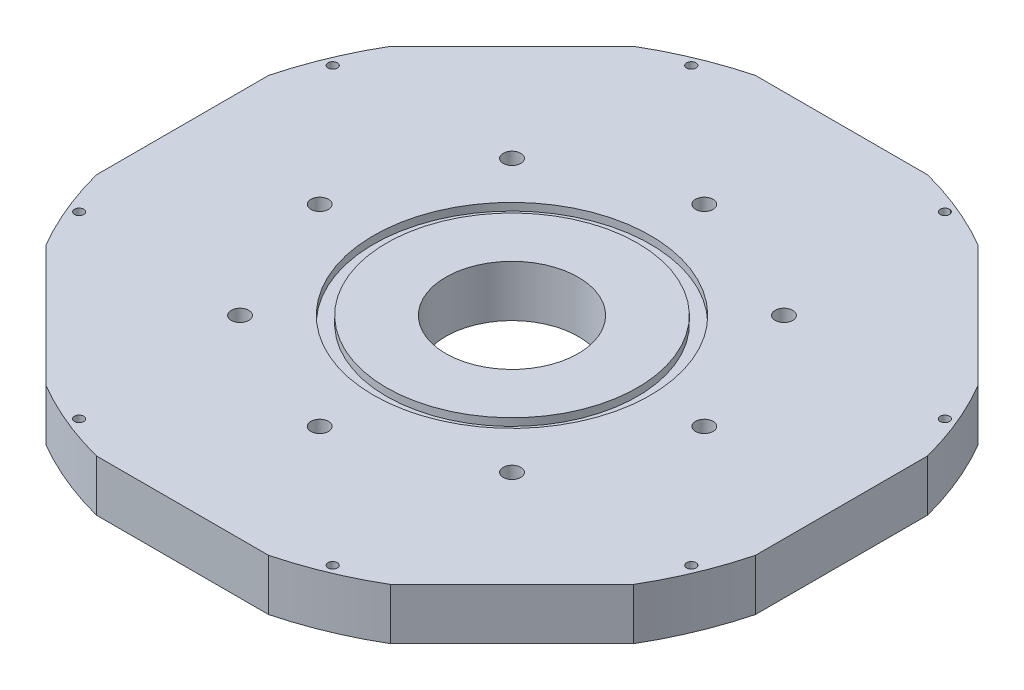
SolidWorks part; units mm, degrees
material "6061-T4 (SS)"
ref_plane "Front Plane" through (0, 0, 0) normal (0, 0, 1) x (1, 0, 0)
ref_plane "Top Plane" through (0, 0, 0) normal (0, 1, 0) x (1, 0, 0)
ref_plane "Right Plane" through (0, 0, 0) normal (1, 0, 0) x (0, 0, -1)
sketch "Sketch1" plane through (0, 0, 0) normal (0, 1, 0) x (1, 0, 0)
  line L1 (-50.6583, 122.3) -> (-122.3, 50.6583)
  line L2 (-122.3, 50.6583) -> (-122.3, -50.6583)
  line L3 (-122.3, -50.6583) -> (-50.6583, -122.3)
  line L4 (-50.6583, -122.3) -> (50.6583, -122.3)
  line L5 (50.6583, -122.3) -> (122.3, -50.6583)
  line L6 (122.3, -50.6583) -> (122.3, 50.6583)
  line L7 (122.3, 50.6583) -> (50.6583, 122.3)
  line L8 (50.6583, 122.3) -> (-50.6583, 122.3)
  circle A0 centre (0, 0) radius 122.3 construction
  circle A1 centre (0, 0) radius 126.4
  dimension "D2" = 252.8
  dimension "D1" = 244.6
extrude "Boss-Extrude1" add sketch "Sketch1" along normal blind 19.05 contours L4 A1 L5 L6 L7 L8 L1 L2 L3 region at (0, 0, 0)
sketch "Sketch3" plane through (0, 19.05, 0) normal (0, 1, 0) x (1, 0, 0)
  circle A0 centre (0, 0) radius 24.5745
  dimension "D1" = 49.149
extrude "Cut-Extrude1" cut sketch "Sketch3" against normal through all contours A0
sketch "Sketch5" plane through (0, 19.05, 0) normal (0, 1, 0) x (1, 0, 0)
  circle A0 centre (0, 0) radius 46.5455
  circle A1 centre (0, 0) radius 51.3715
  dimension "D1" = 93.091
  dimension "D2" = 102.743
extrude "Cut-Extrude2" cut sketch "Sketch5" against normal blind 2.794
sketch "Sketch19" plane through (0, 19.05, 0) normal (0, 1, 0) x (1, 0, 0)
  line L0 (-115.3833, 47.7933) -> (-116.7784, 48.3712)
  line L1 (-119.5501, 41.6796) -> (-111.6676, 60.7097) construction
  line L2 (-116.9739, 43.9532) -> (-114.6894, 49.4685) construction
  line L3 (-122.3, 31.9323) -> (-109.0587, 63.8996) construction
  line L5 (-63.8996, 109.0587) -> (-31.9323, 122.3) construction
  line L6 (-47.916, 115.6793) -> (-43.6974, 105.4949) construction
  circle A0 centre (-113.7876, 47.1324) radius 1.7272
  arc A1 (-109.0587, 63.8996) -> (-122.3, 31.9323) centre (0, 0) ccw construction
  arc A2 (-109.0587, 63.8996) -> (-122.3, 31.9323) centre (0, 0) ccw
  circle A4 centre (0, 0) radius 122.9618
  circle A5 centre (-47.0555, 113.6019) radius 1.7272
  point P9 (-115.6793, 47.916)
  point P10 (-115.3833, 47.7933)
  point P16 (0, 0)
  dimension "D1" = 3.4544
  dimension "D3" = 245.9237
  dimension "D4" = 3.4544
  dimension "D2" = 1.51
extrude "Cut-Extrude4" cut sketch "Sketch19" against normal through all contours A4 A5 | A4 A5 region at (-47.3351, 19.05, -114.2772) region at (-46.7741, 19.05, -112.9227)
pattern_circular "CirPattern2" count 8 over 360 about axis through (0, 0, 0) along (0, 1, 0) of "Cut-Extrude4"
sketch "Sketch21" plane through (0, 19.05, 0) normal (0, 1, 0) x (1, 0, 0)
  point P0 (-71.374, 0)
  dimension "D1" = 71.374
hole_wizard "5/16-18 Tapped Hole2" positions "Sketch22" profile "Sketch23" tap size "5/16-18" standard "ANSI Inch"
sketch "Sketch22" plane through (0, 19.05, 0) normal (0, 1, 0) x (1, 0, 0)
  point P0 (-71.374, 0)
sketch "Sketch23" plane through (-71.374, 19.05, 0) normal (1, 0, 0) x (0, 0, 1)
  line L0 (0, 0) -> (0, 14.6611)
  line L1 (0, 14.6611) -> (3.2639, 12.7)
  line L2 (3.2639, 12.7) -> (3.2639, 0)
  line L5 (3.2639, 0) -> (0, 0)
  line L10 (0, 14.6611) -> (-3.2639, 12.7) construction
  line L11 (0, -6.35) -> (0, 107.95) construction
  dimension "Tap Drill Dia." = 6.5278
  dimension "Tap Drill Depth" = 12.7
  dimension "Drill Angle" = 118
cosmetic thread "Hole Thread2" parameters "D1"=12.7, "D2"=7.9375
sketch "Sketch33" [suppressed] plane through (0, 19.05, 0) normal (0, 1, 0) x (1, 0, 0)
  circle A0 centre (-71.374, 0) radius 3.9687
  dimension "D1" = 7.9375
sketch "Sketch37" plane through (0, 0, 0) normal (0, -1, 0) x (1, 0, 0)
  circle A0 centre (0, 0) radius 119.0625
  circle A1 centre (0, 0) radius 115.2525
  dimension "D1" = 238.125
  dimension "D2" = 230.505
extrude "Cut-Extrude7" cut sketch "Sketch37" against normal blind 2.667
pattern_circular "CirPattern4" count 8 over 360 about axis through (0, 0, 0) along (0, 1, 0) of "5/16-18 Tapped Hole2" reverse direction yes
cosmetic thread "Hole Thread3" parameters "D1"=12.7, "D2"=7.9375
cosmetic thread "Hole Thread4" parameters "D1"=12.7, "D2"=7.9375
cosmetic thread "Hole Thread5" parameters "D1"=12.7, "D2"=7.9375
cosmetic thread "Hole Thread6" parameters "D1"=12.7, "D2"=7.9375
cosmetic thread "Hole Thread7" parameters "D1"=12.7, "D2"=7.9375
cosmetic thread "Hole Thread8" parameters "D1"=12.7, "D2"=7.9375
cosmetic thread "Hole Thread9" parameters "D1"=12.7, "D2"=7.9375
